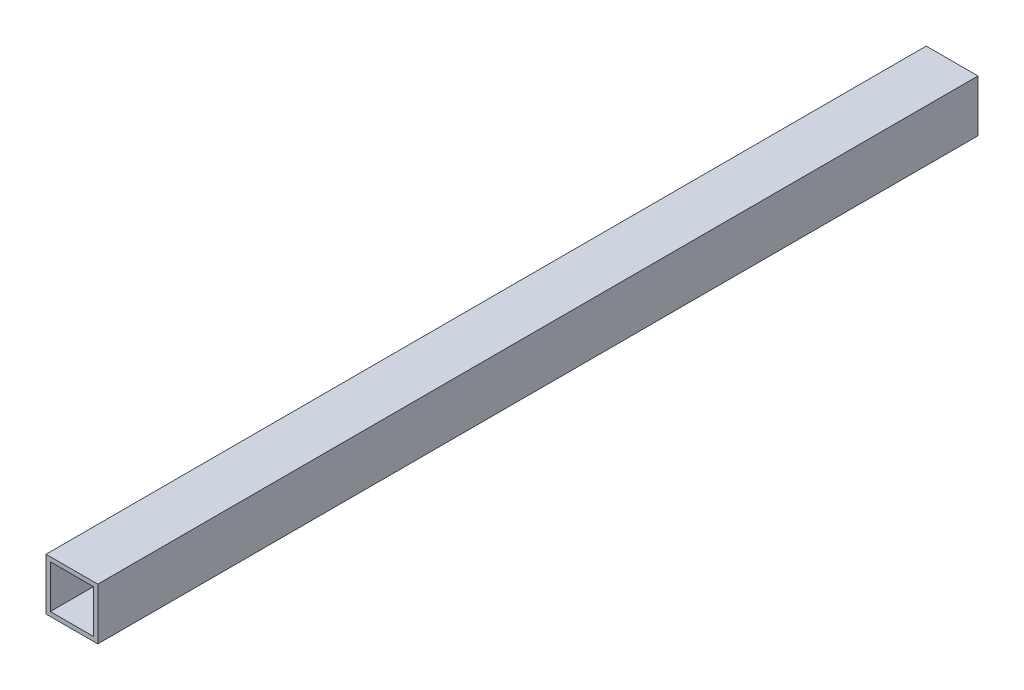
SolidWorks part; units mm, degrees
material "6061 Alloy"
ref_plane "Front Plane" through (0, 0, 0) normal (0, 0, 1) x (1, 0, 0)
ref_plane "Top Plane" through (0, 0, 0) normal (0, 1, 0) x (1, 0, 0)
ref_plane "Right Plane" through (0, 0, 0) normal (1, 0, 0) x (0, 0, -1)
sketch "Sketch1" plane through (0, 0, 0) normal (0, 0, 1) x (1, 0, 0)
  line L1 (-7.9375, -7.9375) -> (7.9375, -7.9375)
  line L2 (-7.9375, -7.9375) -> (-7.9375, 7.9375)
  line L3 (-7.9375, 7.9375) -> (7.9375, 7.9375)
  line L4 (7.9375, -7.9375) -> (7.9375, 7.9375)
  line L5 (-7.9375, -7.9375) -> (7.9375, 7.9375) construction
  line L6 (-7.9375, 7.9375) -> (7.9375, -7.9375) construction
  line L7 (-9.525, -9.525) -> (9.525, -9.525)
  line L8 (-9.525, -9.525) -> (-9.525, 9.525)
  line L9 (-9.525, 9.525) -> (9.525, 9.525)
  line L10 (9.525, -9.525) -> (9.525, 9.525)
  line L11 (-9.525, -9.525) -> (9.525, 9.525) construction
  line L12 (-9.525, 9.525) -> (9.525, -9.525) construction
  point P0 (0, 0)
  point P6 (0, 0)
  dimension "D1" = 19.05
  dimension "D2" = 19.05
  dimension "D3" = 1.5875
  dimension "D4" = 1.5875
extrude "Boss-Extrude1" add sketch "Sketch1" along normal mid plane 323.85
